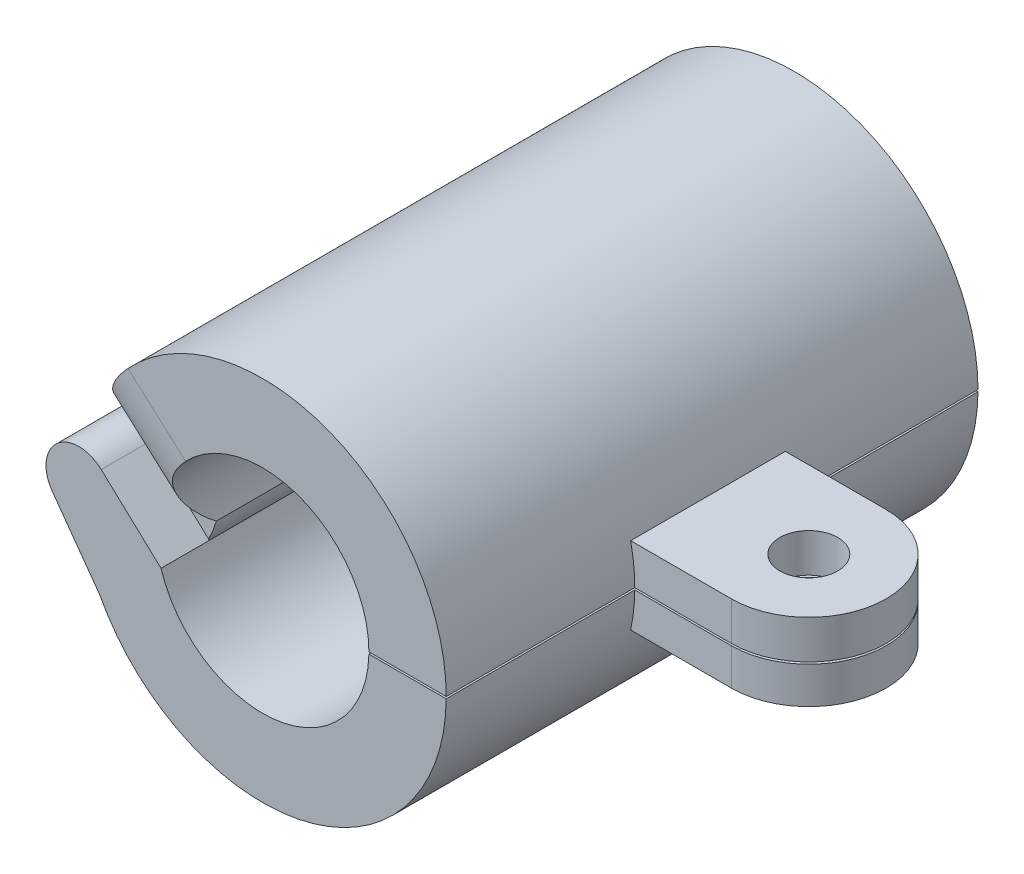
SolidWorks part; units mm, degrees
ref_plane "Front Plane" through (0, 0, 0) normal (0, 0, 1) x (1, 0, 0)
ref_plane "Top Plane" through (0, 0, 0) normal (0, 1, 0) x (1, 0, 0)
ref_plane "Right Plane" through (0, 0, 0) normal (1, 0, 0) x (0, 0, -1)
sketch "Sketch1" plane through (0, 0, 0) normal (0, 0, 1) x (1, 0, 0)
  circle A0 centre (0, 0) radius 5.5
  circle A1 centre (0, 0) radius 9.5
  dimension "D1" = 11
  dimension "D2" = 4
extrude "Boss-Extrude1" add sketch "Sketch1" along normal mid plane 27.5
sketch "Sketch2" plane through (0, 0, 13.75) normal (0, 0, 1) x (1, 0, 0)
  line L1 (0, 0) -> (9.5, 0)
  line L2 (0, 0) -> (0, -0.1)
  line L3 (0, -0.1) -> (9.5, -0.1)
  line L4 (9.5, 0) -> (9.5, -0.1)
  circle A0 centre (0, 0) radius 9.5 construction
  circle A1 centre (-9.5, 0) radius 1.7
  circle A2 centre (-9.5, 0) radius 1.95
  arc A3 (-8.3075, 4.6082) -> (-7.9968, 1.2421) centre (-5.6841, 3.153) ccw
  circle A4 centre (-9.5, 0) radius 4.25
  circle A5 centre (-9.5, 0) radius 4.55
  point P15 (0, 0)
  dimension "D2" = 3.4
  dimension "D4" = 3
  dimension "D1" = 0.1
  dimension "D3" = 0.25
  dimension "D5" = 2.3
  dimension "D6" = 0.3
sketch "Sketch3" plane through (0, 0, 13.75) normal (0, 0, 1) x (1, 0, 0)
  line L0 (0, -0.1) -> (9.5, -0.1) construction
  line L1 (0, 0) -> (9.5, 0) construction
  line L2 (0, -0.1) -> (9.5, -0.1)
  line L3 (0, 0) -> (9.5, 0)
  circle A0 centre (-9.5, 0) radius 4.25 construction
  circle A1 centre (-9.5, 0) radius 4.55 construction
  arc A2 (-8.5493, -4.1423) -> (-5.3914, -1.0873) centre (-9.5, 0) ccw
  arc A3 (-8.4104, -4.4176) -> (-5.2525, -1.6313) centre (-9.5, 0) ccw
  circle A4 centre (0, 0) radius 5.5 construction
  circle A5 centre (0, 0) radius 9.5 construction
  arc A6 (-5.3914, -1.0873) -> (-5.2525, -1.6313) centre (0, 0) ccw
  arc A7 (-8.5493, -4.1423) -> (-8.4104, -4.4176) centre (0, 0) ccw
  arc A8 (9.4995, -0.1) -> (9.5, 0) centre (0, 0) ccw
  arc A9 (5.4991, -0.1) -> (5.5, 0) centre (0, 0) ccw
  circle M1 centre (0, 0) radius 9.5
  circle M2 centre (0, 0) radius 5.5
extrude "Cut-Extrude2" cut sketch "Sketch3" against normal through all contours L3 L2 M2 M1 | A3 A2 M1 M2
sketch "Sketch4" plane through (0, 0, 13.75) normal (0, 0, 1) x (1, 0, 0)
  circle A0 centre (-9.5, 0) radius 1.95 construction
  arc A1 (-8.3075, 4.6082) -> (-7.9968, 1.2421) centre (-5.6841, 3.153) ccw construction
  circle A2 centre (-9.5, 0) radius 1.95
  arc A3 (-8.3075, 4.6082) -> (-7.9968, 1.2421) centre (-5.6841, 3.153) ccw
  arc A4 (9.5, 0) -> (-8.5493, -4.1423) centre (0, 0) ccw construction
  arc A5 (-8.3075, 4.6082) -> (-9.2999, 1.9397) centre (0, 0) ccw
  arc M5 (9.5, 0) -> (-8.5493, -4.1423) centre (0, 0) ccw
extrude "Cut-Extrude3" cut sketch "Sketch4" against normal through all contours A3 A2 M5 | A2 M5
sketch "Sketch5" plane through (0, 0, 13.75) normal (0, 0, 1) x (1, 0, 0)
  line L0 (-12.7557, -2.7318) -> (-10.9938, -1.2534) construction
  line L1 (0, 0) -> (9.5, 0) construction
  circle A2 centre (-9.5, 0) radius 1.95
  circle A3 centre (-9.5, 0) radius 4.25
  arc A4 (-10.9938, -1.2534) -> (-12.7557, -2.7318) centre (-11.8747, -1.9926) ccw
  arc A7 (-9.2999, -1.9397) -> (-8.5493, -4.1423) centre (0, 0) ccw construction
  arc A8 (-9.2999, -1.9397) -> (-8.5493, -4.1423) centre (0, 0) ccw
  circle A9 centre (-9.5, 0) radius 1.95 construction
  circle A10 centre (-9.5, 0) radius 4.25 construction
  point P14 (0, 0)
  arc M5 (-9.2999, -1.9397) -> (-8.5493, -4.1423) centre (0, 0) ccw
  dimension "D1" = 140
extrude "Boss-Extrude3" add sketch "Sketch5" against normal through all contours L0 A3 A2 M5 | A4 L0
sketch "Sketch8" plane through (0, 0, 0) normal (0, 0, 1) x (1, 0, 0)
  circle A0 centre (-9.5, 0) radius 1.7 construction
  circle A1 centre (-9.5, 0) radius 1.7
extrude "Boss-Extrude4" add sketch "Sketch8" along normal through all and the other way through all separate body
sketch "Sketch9" plane through (0, 0, 13.75) normal (0, 0, 1) x (1, 0, 0)
  line L0 (-8.4104, -4.4176) -> (-10.8789, -0.9943)
  line L1 (-5.2525, -1.6313) -> (-8.3417, 1.2443)
  circle A0 centre (-9.5, 0) radius 1.7 construction
  circle A1 centre (-9.5, 0) radius 4.55 construction
  arc A2 (-8.4104, -4.4176) -> (-5.2525, -1.6313) centre (-9.5, 0) ccw
  arc A3 (-10.8789, -0.9943) -> (-8.3417, 1.2443) centre (-9.5, 0) ccw
extrude "Boss-Extrude5" add sketch "Sketch9" against normal blind 2.5
mirror "Mirror1" about plane through (0, 0, 0) normal (0, 0, 1) of "Boss-Extrude5"
sketch "Sketch11" plane through (0, 0, 13.75) normal (0, 0, 1) x (1, 0, 0)
  line L0 (-7.9968, 1.2421) -> (-5.3914, -1.0873)
  line L1 (5.5, 0) -> (9.5, 0)
  arc A6 (9.5, 0) -> (-8.3075, 4.6082) centre (0, 0) ccw
  arc A7 (-8.3075, 4.6082) -> (-7.9968, 1.2421) centre (-5.6841, 3.153) ccw
  arc A8 (-10.9938, -1.2534) -> (-7.9968, 1.2421) centre (-9.5, 0) ccw
  arc A9 (-10.9938, -1.2534) -> (-12.7557, -2.7318) centre (-11.8747, -1.9926) ccw
  arc A10 (-12.7557, -2.7318) -> (-5.3914, -1.0873) centre (-9.5, 0) ccw
  arc A11 (5.5, 0) -> (-5.3914, -1.0873) centre (0, 0) ccw
  arc A14 (-10.9938, -1.2534) -> (-7.9968, 1.2421) centre (-9.5, 0) ccw
  arc A15 (-10.9938, -1.2534) -> (-12.7557, -2.7318) centre (-11.8747, -1.9926) ccw
  arc A16 (-12.7557, -2.7318) -> (-5.3914, -1.0873) centre (-9.5, 0) ccw
  dimension "D1" = 0
extrude "Cut-Extrude4" cut sketch "Sketch11" against normal blind 3
mirror "Mirror2" about plane through (0, 0, 0) normal (0, 0, 1) of "Cut-Extrude4"
fillet "Fillet1" radius 5 2 edges at (-6.6941, 0.0774, 13.75) (-6.6941, 0.0774, -13.75)
sketch "Sketch12" plane through (0, 0, 0) normal (0, 1, 0) x (1, 0, 0)
  line L0 (4.5, 0) -> (14.5, 0) construction
  line L1 (4.5, 4) -> (14.5, 4)
  line L2 (4.5, -4) -> (14.5, -4)
  line L3 (9.5, 13.75) -> (9.5, -13.75) construction
  line L4 (5.4991, 13.75) -> (5.4991, -13.75) construction
  line L5 (5.4991, 13.75) -> (5.4991, -13.75)
  arc A0 (4.5, 4) -> (4.5, -4) centre (4.5, 0) ccw
  arc A1 (14.5, -4) -> (14.5, 4) centre (14.5, 0) ccw
  point P2 (9.5, 0)
  point P11 (0, 0)
  dimension "D1" = 4
  dimension "D2" = 10
extrude "Boss-Extrude6" add sketch "Sketch12" along normal mid plane 4
sketch "Sketch13" plane through (0, 0, 4) normal (0, 0, 1) x (1, 0, 0)
  line L1 (5.4991, -0.1) -> (19.0226, -0.1)
  line L2 (5.4991, -0.1) -> (5.4991, 0)
  line L3 (5.4991, 0) -> (19.0226, 0)
  line L4 (19.0226, -0.1) -> (19.0226, 0)
extrude "Cut-Extrude5" cut sketch "Sketch13" against normal through all
hole_wizard "Ø1.0mm Dowel Hole1" positions "3DSketch1" profile "Sketch15" hole size "Ø1.0" standard "ANSI Metric"
sketch3d "3DSketch1"
  line L0 (14.5, 2, 0) -> (14.5, 0, 0) construction
  point P0 (14.5, 2, 0)
sketch "Sketch15" plane through (14.5, 2, 0) normal (1, 0, 0) x (0, 0, 1)
  line L0 (0, 0) -> (0, 50)
  line L1 (0, 50) -> (1.5, 49.0987)
  line L2 (1.5, 49.0987) -> (1.5, 0)
  line L5 (1.5, 0) -> (0, 0)
  line L10 (0, 50) -> (-1.5, 49.0987) construction
  line L11 (0, -6.35) -> (0, 107.95) construction
  dimension "Hole Dia." = 3
  dimension "Hole Depth" = 50
  dimension "Drill Angle" = 118
